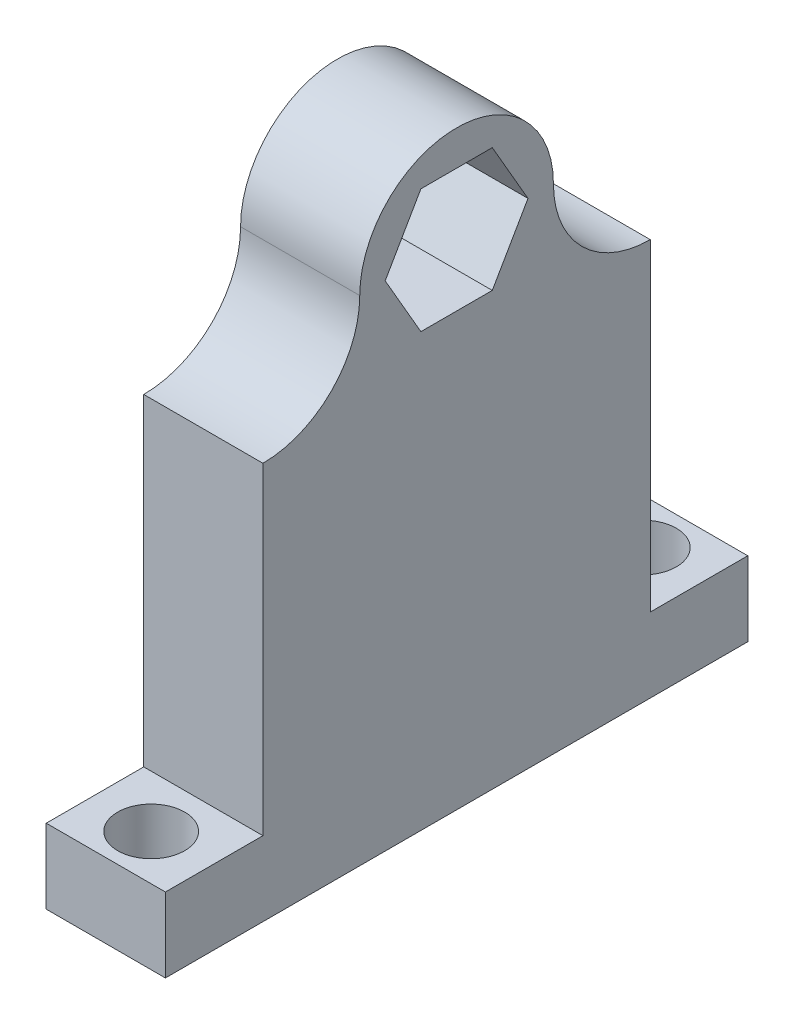
SolidWorks part; units mm, degrees
ref_plane "Спереди" through (0, 0, 0) normal (0, 0, 1) x (1, 0, 0)
ref_plane "Сверху" through (0, 0, 0) normal (0, 1, 0) x (1, 0, 0)
ref_plane "Справа" through (0, 0, 0) normal (1, 0, 0) x (0, 0, -1)
sketch "Эскиз1" plane through (0, 0, 0) normal (1, 0, 0) x (0, 0, -1)
  line L6 (-6.5, 0) -> (6.5, 0) construction
  line L12 (-13, -6.5) -> (-13, -11.5)
  line L13 (13, -6.5) -> (13, -11.5)
  line L15 (-13, -11.5) -> (13, -11.5)
  arc A0 (6.5, 0) -> (-6.5, 0) centre (0, 0) ccw
  arc A1 (-13, -6.5) -> (-6.5, 0) centre (-13, 0) ccw
  arc A2 (6.5, 0) -> (13, -6.5) centre (13, 0) ccw
  point P4 (0, 0)
  point P7 (0, -39.795)
  point P9 (0, 6.5)
  dimension "D1" = 13
  dimension "D4" = 13
  dimension "D5" = 13
  dimension "D2" = 5
extrude "Бобышка-Вытянуть1" add sketch "Эскиз1" along normal blind 8
sketch "Эскиз2" plane through (8, 0, 0) normal (1, 0, 0) x (0, 0, -1)
  line L1 (4.792, 0) -> (2.396, 4.15)
  line L2 (2.396, 4.15) -> (-2.396, 4.15)
  line L3 (-2.396, 4.15) -> (-4.792, 0)
  line L4 (-4.792, 0) -> (-2.396, -4.15)
  line L5 (-2.396, -4.15) -> (2.396, -4.15)
  line L6 (2.396, -4.15) -> (4.792, 0)
  circle A0 centre (0, 0) radius 4.15 construction
  dimension "D1" = 8.3
extrude "Вырез-Вытянуть1" cut sketch "Эскиз2" against normal through all
sketch "Эскиз4" plane through (0, -11.5, 0) normal (0, -1, 0) x (1, 0, 0)
  line L8 (0, 13) -> (0, -13)
  line L9 (0, -13) -> (8, -13)
  line L10 (8, -13) -> (8, 13)
  line L11 (8, 13) -> (0, 13)
  line L12 (0, 13) -> (0, -13)
  line L13 (0, -13) -> (8, -13)
  line L14 (8, -13) -> (8, 13)
  line L15 (8, 13) -> (0, 13)
  dimension "D1" = 0
extrude "Бобышка-Вытянуть2" add sketch "Эскиз4" along normal up to surface (21.65 mm away)
sketch "Эскиз5" plane through (0, -33.15, 0) normal (0, -1, 0) x (1, 0, 0)
  line L0 (0, 13) -> (0, -13) construction
  line L1 (0, 19.5455) -> (8, 19.5455)
  line L2 (0, 19.5455) -> (0, -19.5455)
  line L3 (0, -19.5455) -> (8, -19.5455)
  line L4 (8, 19.5455) -> (8, -19.5455)
  line L5 (8, -13) -> (8, 13) construction
  line L6 (532.5872, -19.5455) -> (-11.4128, -19.5455) construction
  line L7 (532.5872, 19.5455) -> (-11.4128, 19.5455) construction
  line L8 (4, -16.5) -> (4, 16.5) construction
  line L9 (8, -19.5455) -> (0, 19.5455) construction
  line L10 (0, -19.5455) -> (8, 19.5455) construction
  circle A0 centre (4, -16.5) radius 2.25
  circle A1 centre (4, 16.5) radius 2.25
  point P16 (4, 0)
  point P17 (8, 0)
  point P18 (4, 0)
  dimension "D1" = 4.5
  dimension "D2" = 4.5
  dimension "D3" = 33
extrude "Бобышка-Вытянуть3" add sketch "Эскиз5" against normal blind 5
